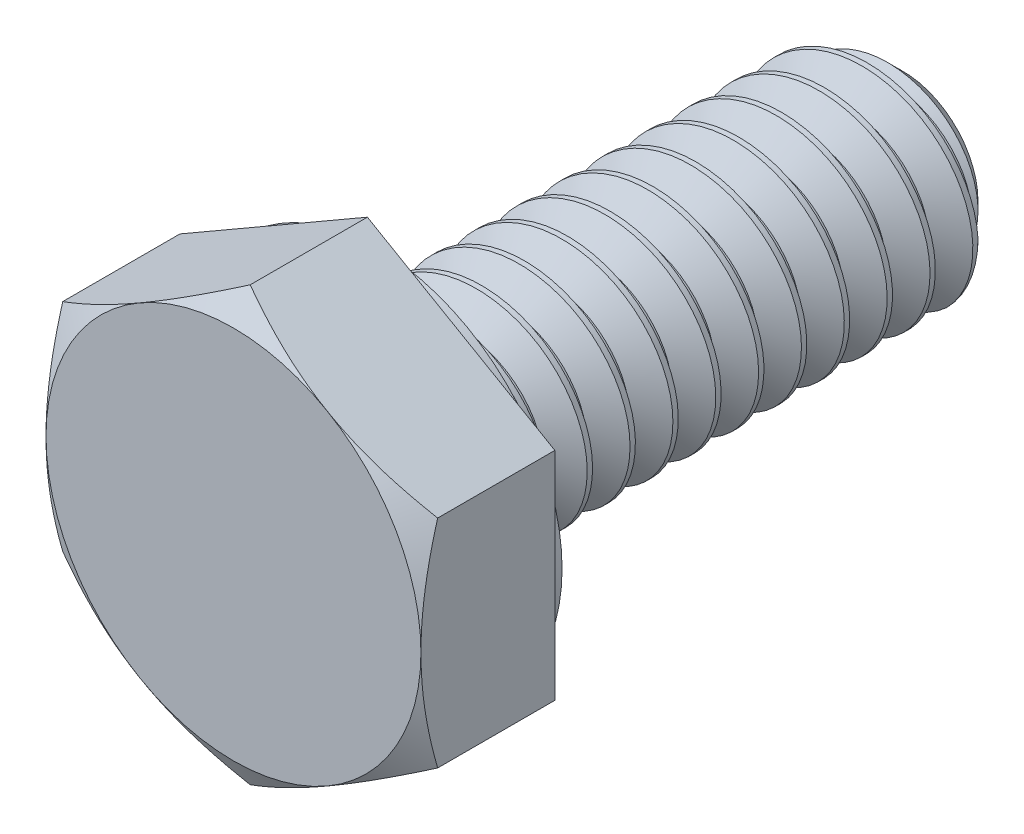
SolidWorks part; units mm, degrees
ref_plane "Front Plane" through (0, 0, 0) normal (0, 0, 1) x (1, 0, 0)
ref_plane "Top Plane" through (0, 0, 0) normal (0, 1, 0) x (1, 0, 0)
ref_plane "Right Plane" through (0, 0, 0) normal (1, 0, 0) x (0, 0, -1)
sketch "Sketch1" plane through (0, 0, 0) normal (1, 0, 0) x (0, 0, -1)
  line L0 (0, 0) -> (15.875, 0) construction
  line L1 (15.875, 3.175) -> (15.875, -3.175) construction
  line L2 (0, 5.5563) -> (0, -5.5563) construction
  line L3 (0, 0) -> (-3.9687, 0) construction
  line L4 (-3.9688, 5.5563) -> (-3.9687, -5.5562) construction
  line L5 (15.7956, 3.3125) -> (17.0656, 3.3125) construction
  line L6 (17.0656, 3.3125) -> (16.4306, 2.2126) construction
  line L7 (16.4306, 2.2126) -> (15.7956, 3.3125) construction
  line L8 (15.8353, 3.2437) -> (17.0259, 3.2437) construction
  line L9 (15.875, 3.175) -> (16.9863, 3.175) construction
  line L10 (16.3512, 2.3501) -> (16.51, 2.3501) construction
  line L11 (16.4306, 3.3125) -> (16.4306, 3.175) construction
  line L12 (16.4306, 2.3501) -> (16.4306, 2.2126) construction
  point P5 (15.875, 0)
  point P9 (0, 0)
  point P13 (-3.9687, 0)
  point P18 (12.7, -3.175)
  point P25 (16.4306, 3.2437)
  dimension "Length" = 15.875
  dimension "Thread OD" = 6.35
  dimension "Hex Width" = 11.1125
  dimension "Hex Height" = 3.9688
  dimension "D1" = 60
  dimension "Pitch" = 1.27
  dimension "D2" = 0.1588
  dimension "D3" = 3.175
sketch "Sketch2" plane through (0, 0, 0) normal (1, 0, 0) x (0, 0, -1)
  line L0 (0, 0) -> (15.875, 0)
  line L1 (0, 5.5563) -> (0, -5.5563) construction
  line L2 (15.875, 0) -> (15.875, 3.175)
  line L3 (15.875, 3.175) -> (0, 3.175)
  line L4 (0, 3.175) -> (0, 0)
revolve "Revolve1" add sketch "Sketch2" angle 360 about L0
sketch "Sketch3" plane through (0, 0, 0) normal (0, 0, 1) x (1, 0, 0)
  line L1 (0, 6.4158) -> (-5.5562, 3.2079)
  line L2 (-5.5562, 3.2079) -> (-5.5562, -3.2079)
  line L3 (-5.5562, -3.2079) -> (0, -6.4158)
  line L4 (0, -6.4158) -> (5.5562, -3.2079)
  line L5 (5.5562, -3.2079) -> (5.5562, 3.2079)
  line L6 (5.5562, 3.2079) -> (0, 6.4158)
  circle A0 centre (0, 0) radius 5.5563 construction
extrude "Boss-Extrude1" add sketch "Sketch3" along normal up to vertex (3.9688 mm away) up to point (0, 0, 3.9687)
sketch "Sketch7" plane through (0, 0, 0) normal (0, 0, -1) x (-1, 0, 0)
  circle A4 centre (0, 0) radius 5.4928
  circle A5 centre (0, 0) radius 5.4928
  dimension "D1" = 0.0635
extrude "Boss-Extrude2" add sketch "Sketch7" along normal blind 0.2778
chamfer "Chamfer1" distance 0.9525 angle 45 1 edges at (3.175, 0, -15.875)
sketch "Sketch4" plane through (0, 0, 3.9687) normal (0, 0, 1) x (1, 0, 0)
  circle A0 centre (0, 0) radius 5.5563
extrude "Cut-Extrude1" cut sketch "Sketch4" against normal through all draft 60 flip side to cut
ref_axis "Center Axis 1" through (0, 0, -40.7048) along (0, 0, 1)
split "Split1" bodies to split 106 resulting bodies 107 108 split by face at (5.4928, 0, 0)
sketch "Sketch5" plane through (0, 0, 0) normal (1, 0, 0) x (0, 0, -1)
  line L0 (15.8353, 3.2437) -> (17.0259, 3.2437)
  line L1 (15.8353, 3.2437) -> (16.3512, 2.3501)
  line L2 (16.3512, 2.3501) -> (16.51, 2.3501)
  line L3 (17.0259, 3.2437) -> (16.51, 2.3501)
sketch "Sketch6" plane through (0, 0, -15.875) normal (0, 0, -1) x (-1, 0, 0)
  circle A0 centre (0, 0) radius 3.175
curve "Helix/Spiral1" pitch 1.27 height 17.145 radius 3.175 centre (0, 0, -15.875) axis (0, 0, 1) start towards (0, 1, 0)
sweep "Cut-Sweep1" cut profiles "Sketch5" path "Helix/Spiral1" align with end faces yes
combine bodies "Combine1" operation type add bodies to combine 108 109
sketch "Sketch8" plane through (0, 0, -0.2778) normal (0, 0, -1) x (-1, 0, 0)
  circle A0 centre (0, 0) radius 5.4928 construction
  circle A1 centre (0, 0) radius 5.4928
extrude "Boss-Extrude3" add sketch "Sketch8" against normal up to surface (0.2778 mm away) up to face at (0.3017, 1.2846, 0)
equation "\"D2@Sketch1\"=\"Pitch@Sketch1\"/8"
equation "\"D1@Chamfer1\"=\"Pitch@Sketch1\"*.75"
equation "\"D4@Helix/Spiral1\"=\"Pitch@Sketch1\""
equation "\"D3@Helix/Spiral1\"=\"Length@Sketch1\"+\"Pitch@Sketch1\""
equation "\"D3@Sketch1\"=\"Pitch@Sketch1\"*2.5"
equation "\"D1@Boss-Extrude2\"=\"Hex Width@Sketch1\"*.025"
